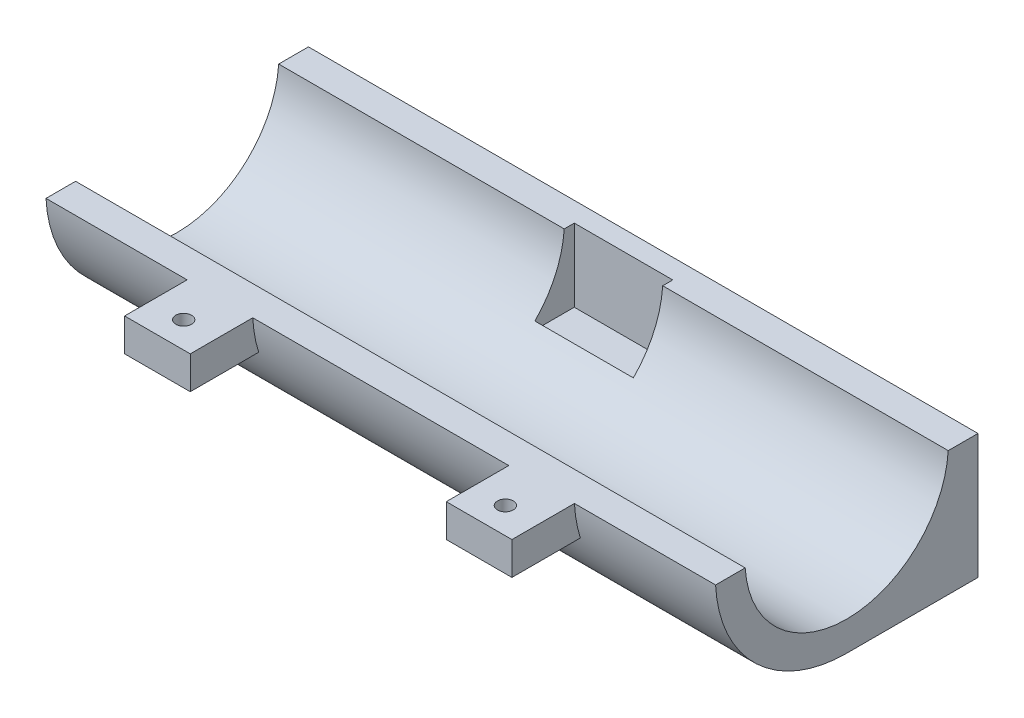
SolidWorks part; units mm, degrees
ref_plane "Front Plane" through (0, 0, 0) normal (0, 0, 1) x (1, 0, 0)
ref_plane "Top Plane" through (0, 0, 0) normal (0, 1, 0) x (1, 0, 0)
ref_plane "Right Plane" through (0, 0, 0) normal (1, 0, 0) x (0, 0, -1)
sketch "Sketch1" plane through (0, 0, 0) normal (1, 0, 0) x (0, 0, -1)
  line L1 (-20.9452, 21.1459) -> (13.0548, 21.1459)
  line L2 (-20.9452, 21.1459) -> (-20.9452, -8.8541)
  line L3 (-20.9452, -8.8541) -> (13.0548, -8.8541)
  line L4 (13.0548, 21.1459) -> (13.0548, -8.8541)
  dimension "D1" = 34
  dimension "D2" = 30
extrude "Boss-Extrude2" add sketch "Sketch1" along normal blind 51
sketch "Sketch3" plane through (0, 0, -13.0548) normal (0, 0, -1) x (-1, 0, 0)
  line L0 (-51, -8.8541) -> (0, -8.8541) construction
  line L1 (-51, -8.8541) -> (-51, 21.1459) construction
  circle A0 centre (-25.5, -1.3541) radius 2.55
  point P2 (-25.5, -8.8541)
  dimension "D1" = 7.5
  dimension "D2" = 5.1
  dimension "D3" = 25.5
extrude "Cut-Extrude3" cut sketch "Sketch3" against normal blind 10
sketch "Sketch5" plane through (51, 0, 0) normal (1, 0, 0) x (0, 0, -1)
  line L0 (13.0548, -8.8541) -> (13.0548, 21.1459) construction
  line L1 (-20.9452, -8.8541) -> (13.0548, -8.8541) construction
  circle A0 centre (-3.9452, 1.1459) radius 7.75
  dimension "D1" = 17
  dimension "D2" = 10
extrude "Cut-Extrude4" cut sketch "Sketch5" against normal blind 51
sketch "Sketch6" plane through (51, 0, 0) normal (1, 0, 0) x (0, 0, -1)
  line L0 (-20.9452, -8.8541) -> (13.0548, -8.8541) construction
  line L1 (13.0548, 21.1459) -> (6.0548, 21.1459)
  line L2 (13.0548, 21.1459) -> (13.0548, -8.8541)
  line L3 (13.0548, -8.8541) -> (6.0548, -8.8541)
  line L4 (6.0548, 21.1459) -> (6.0548, -8.8541)
  dimension "D1" = 7
extrude "Cut-Extrude6" cut sketch "Sketch6" against normal blind 51
sketch "Sketch7" plane through (51, 0, 0) normal (1, 0, 0) x (0, 0, -1)
  line L1 (-3.9452, -8.8541) -> (-20.9452, -8.8541)
  line L2 (6.0548, 1.1459) -> (6.0548, 21.1459)
  line L3 (6.0548, 21.1459) -> (-20.9452, 21.1459)
  line L4 (-20.9452, -8.8541) -> (-20.9452, 21.1459)
  arc A0 (6.0548, 1.1459) -> (-3.9452, -8.8541) centre (-3.9452, 1.1459) ccw
extrude "Cut-Extrude7" cut sketch "Sketch7" against normal blind 51
sketch "Sketch8" plane through (0, 0, -3.0548) normal (0, 0, -1) x (-1, 0, 0)
  line L2 (-21.75, -2.1801) -> (-21.75, -4.9041)
  line L3 (-21.75, -4.9041) -> (-29.25, -4.9041)
  line L4 (-29.25, -2.1801) -> (-29.25, -4.9041)
  line L6 (-29.25, -2.1801) -> (-29.25, 2.1959)
  line L7 (-29.25, 2.1959) -> (-21.75, 2.1959)
  line L8 (-21.75, -2.1801) -> (-21.75, 2.1959)
  arc A0 (-27.9125, -2.1801) -> (-23.0875, -2.1801) centre (-25.5, -1.3541) ccw construction
  arc A1 (-24.9975, 1.1459) -> (-26.0025, 1.1459) centre (-25.5, -1.3541) ccw construction
  point P4 (-25.5, -3.9041)
  point P8 (-25.5, -3.9041)
  point P11 (-25.5, 1.1959)
  dimension "D1" = 7.5
  dimension "D2" = 3.75
  dimension "D3" = 1
  dimension "D4" = 1
extrude "Cut-Extrude9" cut sketch "Sketch8" against normal blind 1.5 and the other way blind 1.5
sketch "Sketch10" plane through (51, 0, 0) normal (1, 0, 0) x (0, 0, -1)
  line L1 (-17.6952, 1.1459) -> (-17.6952, 4.1459)
  line L2 (-17.6952, 4.1459) -> (-11.6952, 4.1459)
  line L3 (-11.6952, 4.1459) -> (-11.6952, 1.1459)
  line L4 (-11.6952, -1.8541) -> (-17.6952, -1.8541)
  line L5 (-17.6952, -1.8541) -> (-17.6952, 1.1459)
  line L6 (-11.6952, -1.8541) -> (-11.6952, 1.1459)
  circle A0 centre (-3.9452, 1.1459) radius 7.75 construction
  dimension "D1" = 3
  dimension "D2" = 3
  dimension "D3" = 6
extrude "Boss-Extrude5" add sketch "Sketch10" against normal blind 51
sketch "Sketch11" plane through (51, 0, 0) normal (1, 0, 0) x (0, 0, -1)
  line L0 (-13.4846, -1.8541) -> (-17.6952, -1.8541)
  line L1 (-17.6952, -1.8541) -> (-17.6952, 4.1459)
  line L2 (-17.6952, 4.1459) -> (-13.4846, 4.1459)
  arc A0 (-13.4846, 4.1459) -> (-13.4846, -1.8541) centre (-3.9452, 1.1459) ccw
extrude "Cut-Extrude10" cut sketch "Sketch11" against normal blind 13
sketch "Sketch12" plane through (0, 0, 0) normal (-1, 0, 0) x (0, 0, 1)
  line L0 (13.4846, -1.8541) -> (17.6952, -1.8541)
  line L1 (17.6952, -1.8541) -> (17.6952, 4.1459)
  line L2 (17.6952, 4.1459) -> (13.4846, 4.1459)
  arc A0 (13.4846, -1.8541) -> (13.4846, 4.1459) centre (3.9452, 1.1459) ccw
extrude "Cut-Extrude11" cut sketch "Sketch12" against normal blind 13
sketch "Sketch13" plane through (0, 0, 17.6952) normal (0, 0, 1) x (1, 0, 0)
  line L0 (13, -1.8541) -> (13, 4.1459) construction
  line L1 (24.5, -1.8541) -> (26.5, -1.8541)
  line L2 (24.5, -1.8541) -> (24.5, 4.1459)
  line L3 (24.5, 4.1459) -> (26.5, 4.1459)
  line L4 (26.5, -1.8541) -> (26.5, 4.1459)
  line L5 (38, 4.1459) -> (38, -1.8541) construction
  line L6 (13, 4.1459) -> (38, 4.1459) construction
  line L7 (13, -1.8541) -> (38, -1.8541) construction
  dimension "D1" = 2
  dimension "D2" = 11.5
  dimension "D3" = 11.5
  dimension "D4" = 0
  dimension "D5" = 0
extrude "Cut-Extrude12" cut sketch "Sketch13" against normal blind 2
sketch "Sketch15" plane through (24.5, 0, 0) normal (1, 0, 0) x (0, 0, -1)
  line L0 (-17.6952, 4.1459) -> (-17.6952, -1.8541)
  line L1 (-17.6952, -1.8541) -> (-13.4846, -1.8541)
  line L2 (-13.4846, -1.8541) -> (-17.6952, -1.8541) construction
  line L4 (-13.4846, 4.1459) -> (-17.6952, 4.1459)
  arc A0 (-13.4846, 4.1459) -> (-13.4846, -1.8541) centre (-3.9452, 1.1459) ccw
extrude "Cut-Extrude13" cut sketch "Sketch15" against normal blind 11 and the other way blind 13
sketch "Sketch17" plane through (38, 0, 0) normal (1, 0, 0) x (0, 0, -1)
  line L0 (-13.4846, 4.1459) -> (-17.6952, 4.1459)
  line L1 (-17.6952, 4.1459) -> (-17.6952, -1.8541)
  line L2 (-17.6952, -1.8541) -> (-13.4846, -1.8541)
  arc A0 (-13.4846, 4.1459) -> (-13.4846, -1.8541) centre (-3.9452, 1.1459) ccw
extrude "Boss-Extrude6" add sketch "Sketch17" along normal blind 2.25
sketch "Sketch19" plane through (13, 0, 0) normal (-1, 0, 0) x (0, 0, 1)
  line L0 (13.4846, 4.1459) -> (17.6952, 4.1459)
  line L1 (17.6952, 4.1459) -> (17.6952, -1.8541)
  line L2 (17.6952, -1.8541) -> (13.4846, -1.8541)
  arc A0 (13.4846, -1.8541) -> (13.4846, 4.1459) centre (3.9452, 1.1459) ccw
extrude "Boss-Extrude7" add sketch "Sketch19" along normal blind 2.25
sketch "Sketch20" plane through (13.5, 0, 0) normal (1, 0, 0) x (0, 0, -1)
  line L0 (-17.6952, -1.8541) -> (-17.6952, 4.1459)
  line L1 (-17.6952, 4.1459) -> (-13.4846, 4.1459)
  line L3 (-13.4846, -1.8541) -> (-17.6952, -1.8541)
  arc A0 (-13.4846, 4.1459) -> (-13.4846, -1.8541) centre (-3.9452, 1.1459) ccw
extrude "Boss-Extrude8" add sketch "Sketch20" along normal blind 2.25
sketch "Sketch21" plane through (37.5, 0, 0) normal (-1, 0, 0) x (0, 0, 1)
  line L0 (13.4846, 4.1459) -> (17.6952, 4.1459)
  line L1 (17.6952, 4.1459) -> (17.6952, -1.8541)
  line L2 (17.6952, -1.8541) -> (13.4846, -1.8541)
  line L3 (13.4846, -1.8541) -> (17.6952, -1.8541) construction
  arc A0 (13.4846, -1.8541) -> (13.4846, 4.1459) centre (3.9452, 1.1459) ccw
extrude "Boss-Extrude9" add sketch "Sketch21" along normal blind 2.25
sketch "Sketch22" plane through (0, 0, 17.6952) normal (0, 0, 1) x (1, 0, 0)
  line L1 (35.25, -1.8541) -> (40.25, -1.8541)
  line L2 (35.25, -1.8541) -> (35.25, 4.1459)
  line L3 (35.25, 4.1459) -> (40.25, 4.1459)
  line L4 (40.25, -1.8541) -> (40.25, 4.1459)
extrude "Boss-Extrude10" add sketch "Sketch22" along normal blind 1
sketch "Sketch24" plane through (0, 0, 17.6952) normal (0, 0, 1) x (1, 0, 0)
  line L1 (10.75, -1.8541) -> (15.75, -1.8541)
  line L2 (10.75, -1.8541) -> (10.75, 4.1459)
  line L3 (10.75, 4.1459) -> (15.75, 4.1459)
  line L4 (15.75, -1.8541) -> (15.75, 4.1459)
extrude "Boss-Extrude11" add sketch "Sketch24" along normal blind 1
sketch "Sketch25" plane through (0, 4.1459, 0) normal (0, 1, 0) x (1, 0, 0)
  line L0 (10.75, -18.6952) -> (10.75, -13.4846) construction
  line L1 (15.75, -13.4846) -> (15.75, -18.6952) construction
  line L2 (15.75, -18.6952) -> (10.75, -18.6952) construction
  line L3 (10.75, -13.4846) -> (15.75, -13.4846) construction
  line L4 (40.25, -13.4846) -> (40.25, -18.6952) construction
  circle A0 centre (13.25, -16.6952) radius 0.6
  circle A1 centre (37.75, -16.6952) radius 0.6
  dimension "D1" = 2.5
  dimension "D5" = 2.5
  dimension "D2" = 2.5
  dimension "D3" = 2
  dimension "D4" = 3.2106
extrude "Cut-Extrude14" cut sketch "Sketch25" against normal blind 20
sketch "Sketch26" plane through (0, 0, -6.0548) normal (0, 0, -1) x (-1, 0, 0)
  circle A0 centre (-25.5, -1.3541) radius 2.55
  dimension "D1" = 5.1
extrude "Boss-Extrude12" add sketch "Sketch26" against normal blind 1.5
sketch "Sketch27" plane through (51, 0, 0) normal (1, 0, 0) x (0, 0, -1)
  line L1 (-18.6952, -1.8541) -> (-18.6952, 4.1459) construction
  line L2 (-18.6952, 1.1459) -> (-18.6952, 12.0159)
  line L3 (-18.6952, 12.0159) -> (6.5948, 12.0159)
  line L4 (6.5948, 12.0159) -> (6.5948, 1.1459)
  line L8 (-18.6952, 1.1459) -> (-18.6952, 0.6459)
  line L9 (-18.6952, 0.6459) -> (6.5948, 0.6459)
  line L10 (6.5948, 1.1459) -> (6.5948, 0.6459)
  dimension "D1" = 0.5
extrude "Cut-Extrude16" cut sketch "Sketch27" against normal blind 60
